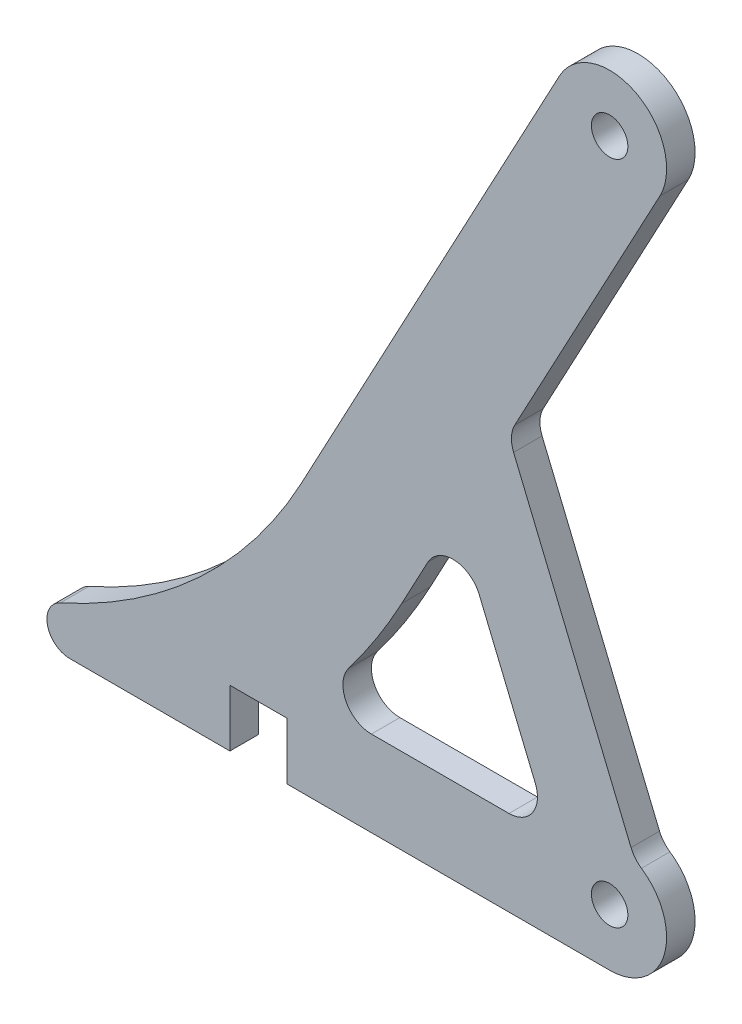
SolidWorks part; units mm, degrees
ref_plane "Front Plane" through (0, 0, 0) normal (0, 0, 1) x (1, 0, 0)
ref_plane "Top Plane" through (0, 0, 0) normal (0, 1, 0) x (1, 0, 0)
ref_plane "Right Plane" through (0, 0, 0) normal (1, 0, 0) x (0, 0, -1)
sketch "Sketch1" plane through (0, 0, 0) normal (0, 0, 1) x (1, 0, 0)
  line L0 (0, 0) -> (0, 105.8361)
  line L1 (0, 0) -> (-88.9, 0)
  line L2 (0, 105.8361) -> (-40.7225, 29.8137)
  line L4 (130.01, 348.5436) -> (-15.875, 76.2) construction
  arc A0 (-88.9, 0) -> (-40.7225, 29.8137) centre (-90.5548, 56.5071) ccw
  dimension "D2" = 88.9
extrude "Boss-Extrude1" add sketch "Sketch1" along normal blind 3.175
fillet "Fillet1" radius 2.54 1 edges at (-88.9, 0, 1.5875)
fillet "Fillet2" radius 6.35 2 edges at (0, 0, 1.5875) (0, 105.8361, 1.5875)
sketch "Sketch2" plane through (0, 0, 3.175) normal (0, 0, 1) x (1, 0, 0)
  circle A0 centre (-6.35, 6.35) radius 2.032
  circle A1 centre (-6.35, 80.5336) radius 2.032
  arc A2 (0, 80.5336) -> (-11.9475, 83.532) centre (-6.35, 80.5336) ccw construction
  arc A3 (-6.35, 0) -> (0, 6.35) centre (-6.35, 6.35) ccw construction
  dimension "D3" = 4.064
extrude "Cut-Extrude1" cut sketch "Sketch2" against normal through all
sketch "Sketch3" plane through (0, 0, 3.175) normal (0, 0, 1) x (1, 0, 0)
  line L0 (-0.7525, 77.5352) -> (-17.6301, 46.0275)
  line L1 (0, 6.35) -> (0, 80.5336) construction
  line L3 (0, 6.35) -> (0, 80.5336)
  line L4 (-39.7054, 9.525) -> (-12.82, 9.525)
  line L6 (-11.9475, 83.532) -> (-40.7225, 29.8137) construction
  line L7 (-29.5275, 23.8169) -> (-23.4441, 35.1737)
  line L8 (-23.4441, 35.1737) -> (-12.82, 9.525)
  line L9 (-66.5345, 0) -> (-6.35, 0) construction
  line L10 (-17.6301, 46.0275) -> (-3.5573, 12.0529)
  line L11 (-15.5503, 16.1166) -> (-6.7504, 19.7616) construction
  line L12 (-11.1504, 17.9391) -> (-6.35, 6.35) construction
  arc A0 (-29.5275, 23.8169) -> (-39.7054, 9.525) centre (-90.5548, 56.5071) cw
  arc A1 (-67.5673, 4.8605) -> (-40.7225, 29.8137) centre (-90.5548, 56.5071) ccw construction
  circle A3 centre (-6.35, 6.35) radius 2.032 construction
  arc A5 (0, 6.35) -> (-3.5573, 12.0529) centre (-6.35, 6.35) ccw
  arc A6 (-0.7525, 77.5352) -> (0, 80.5336) centre (-6.35, 80.5336) ccw
  arc A7 (0, 80.5336) -> (-11.9475, 83.532) centre (-6.35, 80.5336) ccw construction
  point P25 (0, 80.6141)
  point P26 (-1.6722, 75.8797)
  dimension "D1" = 9.525
  dimension "D2" = 12.7
  dimension "D3" = 9.525
  dimension "D4" = 22.5
extrude "Cut-Extrude2" cut sketch "Sketch3" against normal through all
fillet "Fillet3" radius 3.175 5 edges at (-39.7054, 9.525, 1.5875) (-12.82, 9.525, 1.5875) (-23.4441, 35.1737, 1.5875) (-17.6301, 46.0275, 1.5875) (-3.5573, 12.0529, 1.5875)
sketch "Sketch4" plane through (0, 0, 3.175) normal (0, 0, 1) x (1, 0, 0)
  line L0 (-42.3246, 0) -> (-42.3246, 6.35) construction
  line L1 (-48.6746, 0) -> (-42.3246, 0) construction
  line L2 (-48.6746, 6.35) -> (-48.6746, 0) construction
  line L3 (-42.3246, 6.35) -> (-48.6746, 6.35) construction
  line L4 (-42.3246, 0) -> (-42.3246, 6.35)
  line L5 (-48.6746, 0) -> (-42.3246, 0)
  line L6 (-48.6746, 6.35) -> (-48.6746, 0)
  line L7 (-42.3246, 6.35) -> (-48.6746, 6.35)
extrude "Cut-Extrude3" cut sketch "Sketch4" against normal through all
